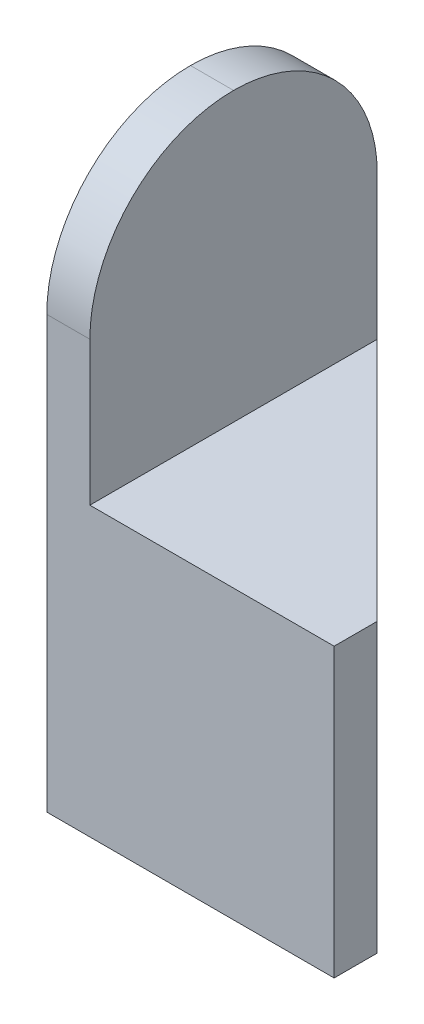
SolidWorks part; units mm, degrees
ref_plane "Спереди" through (0, 0, 0) normal (0, 0, 1) x (1, 0, 0)
ref_plane "Сверху" through (0, 0, 0) normal (0, 1, 0) x (1, 0, 0)
ref_plane "Справа" through (0, 0, 0) normal (1, 0, 0) x (0, 0, -1)
sketch "Эскиз1" plane through (0, 0, 0) normal (0, 1, 0) x (1, 0, 0)
  line L0 (0, 0) -> (0, 20)
  line L1 (0, 20) -> (3, 20)
  line L2 (3, 20) -> (3, 3)
  line L3 (3, 3) -> (20, 3)
  line L4 (20, 3) -> (20, 0)
  line L5 (20, 0) -> (0, 0)
  line L6 (3, 20) -> (20, 3)
  dimension "D1" = 20
  dimension "D2" = 3
extrude "Бобышка-Вытянуть1" add sketch "Эскиз1" along normal mid plane 20 contours L5 L4 L3 L2 L1 L0 region at (0.2828, 0, -10)
extrude "Бобышка-Вытянуть2" add sketch "Эскиз1<3>" along normal blind 3 from offset 10 contours L6 L2 L3 region at (8.6667, 0, -8.6667) offset against normal yes
sketch "Эскиз1<3>" plane through (0, 0, 0) normal (0, 1, 0) x (1, 0, 0) same geometry as "Эскиз1"
mirror "Зеркальное отражение2" about plane through (0, 0, 0) normal (0, 1, 0) of "Бобышка-Вытянуть2"
sketch "Эскиз2" plane through (0, 10, 0) normal (0, 1, 0) x (1, 0, 0)
  line L0 (0, 20) -> (3, 20) construction
  line L1 (0, 0) -> (3, 0)
  line L2 (0, 0) -> (0, 20)
  line L3 (0, 20) -> (3, 20)
  line L4 (3, 0) -> (3, 20)
  line L5 (3, 20) -> (20, 3) construction
  point P6 (3, 20)
extrude "Бобышка-Вытянуть3" add sketch "Эскиз2" along normal blind 20
fillet "Скругление1" radius 10 2 edges at (1.5, 30, 0) (1.5, 30, -20)
